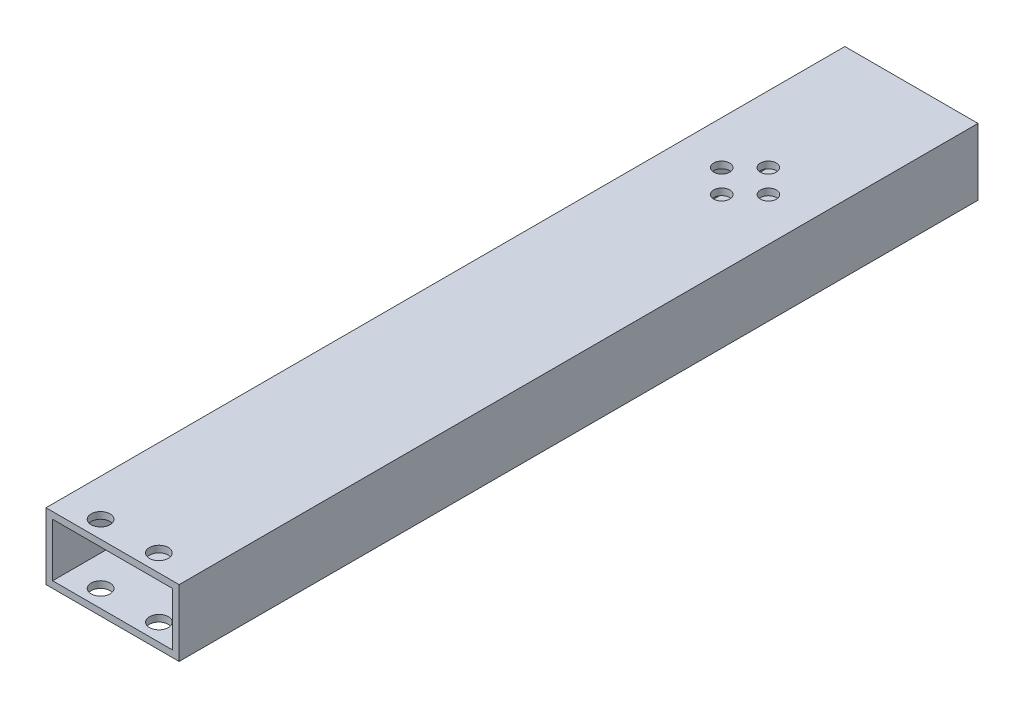
SolidWorks part; units mm, degrees
material "6061 Alloy"
ref_plane "Front Plane" through (0, 0, 0) normal (0, 0, 1) x (1, 0, 0)
ref_plane "Top Plane" through (0, 0, 0) normal (0, 1, 0) x (1, 0, 0)
ref_plane "Right Plane" through (0, 0, 0) normal (1, 0, 0) x (0, 0, -1)
sketch "Sketch1" plane through (0, 0, 0) normal (0, 0, 1) x (1, 0, 0)
  line L1 (-12.7, 6.35) -> (12.7, 6.35)
  line L2 (-12.7, 6.35) -> (-12.7, -6.35)
  line L3 (-12.7, -6.35) -> (12.7, -6.35)
  line L4 (12.7, 6.35) -> (12.7, -6.35)
  point P4 (-12.7, 0)
  point P6 (0, 6.35)
  dimension "D1" = 12.7
  dimension "D2" = 25.4
extrude "Boss-Extrude1" add sketch "Sketch1" along normal blind 127
sketch "Sketch4" plane through (0, 0, 0) normal (0, 0, -1) x (-1, 0, 0)
  line L0 (-12.7, -6.35) -> (-12.7, 6.35) construction
  line L1 (-11.43, 5.08) -> (11.43, 5.08)
  line L2 (-11.43, 5.08) -> (-11.43, -5.08)
  line L3 (-11.43, -5.08) -> (11.43, -5.08)
  line L4 (11.43, 5.08) -> (11.43, -5.08)
  line L5 (-12.7, 6.35) -> (12.7, 6.35) construction
  line L6 (12.7, -6.35) -> (-12.7, -6.35) construction
  line L7 (12.7, 6.35) -> (12.7, -6.35) construction
  dimension "D1" = 1.27
  dimension "D2" = 1.27
  dimension "D3" = 1.27
  dimension "D4" = 1.27
extrude "Cut-Extrude1" cut sketch "Sketch4" against normal through all
sketch "Sketch5" plane through (0, 6.35, 0) normal (0, 1, 0) x (1, 0, 0)
  line L2 (12.7, -127) -> (-12.7, -127) construction
  line L3 (-12.7, -127) -> (-12.7, 0) construction
  circle A0 centre (-5.588, -123.698) radius 1.8034
  circle A1 centre (5.5372, -123.698) radius 1.8034
  dimension "D1" = 3.6068
  dimension "D2" = 3.6068
  dimension "D3" = 11.1252
  dimension "D4" = 7.112
  dimension "D5" = 3.302
  dimension "D6" = 3.302
extrude "Cut-Extrude2" cut sketch "Sketch5" against normal through all both and the other way through all
sketch "Sketch6" plane through (0, -6.35, 0) normal (0, -1, 0) x (-1, 0, 0)
  line L0 (12.7, 0) -> (-12.7, 0) construction
  line L1 (12.7, -127) -> (12.7, 0) construction
  line L2 (12.7, -127) -> (-12.7, -127) construction
  circle A0 centre (4.445, -6.35) radius 1.524
  circle A1 centre (-4.4704, -6.35) radius 1.524
  circle A2 centre (0, -6.35) radius 4.445 construction
  circle A3 centre (0, -1.905) radius 1.524
  circle A4 centre (0, -10.795) radius 1.524
  dimension "D1" = 3.048
  dimension "D2" = 3.048
  dimension "D6" = 8.89
  dimension "D7" = 3.048
  dimension "D8" = 3.048
  dimension "D3" = 8.9154
  dimension "D4" = 6.35
  dimension "D5" = 8.255
  dimension "D9" = 116.205
  dimension "D10" = 120.65
extrude "Cut-Extrude3" cut sketch "Sketch6" against normal through all both contours A3 | A1 | A4 | A0
sketch "Sketch7" plane through (0, 0, 0) normal (0, 0, -1) x (-1, 0, 0)
  line L1 (-12.7, 6.35) -> (12.7, 6.35)
  line L2 (-12.7, 6.35) -> (-12.7, -6.35)
  line L3 (-12.7, -6.35) -> (12.7, -6.35)
  line L4 (12.7, 6.35) -> (12.7, -6.35)
  line L5 (-11.43, 5.08) -> (11.43, 5.08)
  line L6 (-11.43, 5.08) -> (-11.43, -5.08)
  line L7 (-11.43, -5.08) -> (11.43, -5.08)
  line L8 (11.43, 5.08) -> (11.43, -5.08)
extrude "Boss-Extrude2" add sketch "Sketch7" along normal blind 25.4
